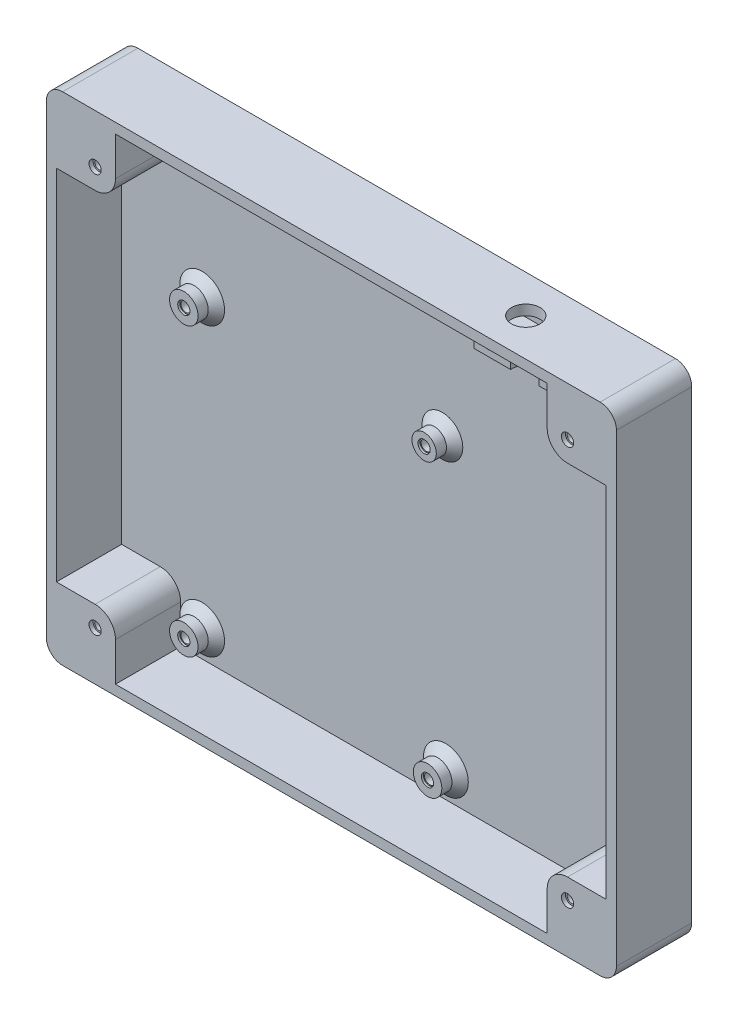
SolidWorks part; units mm, degrees
note: The reader was unsure of these and kept them because the rebuilt part matched: shared geometry of "Croquis1<10>", "Croquis1<11>", "Croquis1<12>", "Croquis1<13>", "Croquis1<14>", "Croquis1<17>".
ref_plane "Alzado" through (0, 0, 0) normal (0, 0, 1) x (1, 0, 0)
ref_plane "Planta" through (0, 0, 0) normal (0, 1, 0) x (1, 0, 0)
ref_plane "Vista lateral" through (0, 0, 0) normal (1, 0, 0) x (0, 0, -1)
sketch "Croquis1" plane through (0, 0, 0) normal (0, 0, 1) x (1, 0, 0)
  line L0 (-40.3571, 102.7463) -> (26.6429, 102.7463)
  line L5 (-40.3571, 102.7463) -> (-40.3571, 24.7463)
  line L6 (-40.3571, 24.7463) -> (26.6429, 24.7463)
  line L7 (26.6429, 102.7463) -> (26.6429, 24.7463)
  line L8 (-40.3571, 102.7463) -> (-34.5972, 102.7463)
  line L9 (26.6429, 102.7463) -> (21.034, 102.7463)
  line L10 (26.6429, 102.7463) -> (26.6429, 99.4658)
  line L11 (26.6429, 24.7463) -> (20.7429, 24.7463)
  line L12 (26.6429, 24.7463) -> (26.6429, 27.9463)
  line L13 (-40.3571, 102.7463) -> (-40.3571, 99.2397)
  line L14 (-40.3571, 24.7463) -> (-34.4345, 24.7463)
  line L15 (-40.3571, 24.7463) -> (-40.3571, 28.5815)
  line L16 (11.3637, 142.2045) -> (11.3637, 20.2045) construction
  line L17 (-41.6363, 129.7045) -> (-41.6363, 141.7045)
  line L26 (-59.1363, 80.7045) -> (80.8637, 80.7045) construction
  line L27 (69.3637, 124.7045) -> (81.3637, 124.7045)
  line L28 (64.3637, 129.7045) -> (64.3637, 141.7045)
  line L29 (69.3637, 36.7045) -> (81.3637, 36.7045)
  line L30 (64.3637, 31.7045) -> (64.3637, 19.7045)
  line L31 (-46.6363, 36.7045) -> (-58.6363, 36.7045)
  line L32 (-41.6363, 31.7045) -> (-41.6363, 19.7045)
  line L39 (81.3637, 137.7045) -> (81.3637, 23.7045)
  line L48 (37.3657, 131.6408) -> (62.3657, 131.6408) construction
  line L53 (37.3657, 134.6408) -> (62.3657, 134.6408)
  line L54 (37.3657, 134.6408) -> (37.3657, 128.6408)
  line L59 (37.3657, 128.6408) -> (62.3657, 128.6408)
  line L60 (62.3657, 134.6408) -> (62.3657, 128.6408)
  line L61 (37.3657, 134.6408) -> (62.3657, 128.6408) construction
  line L62 (37.3657, 128.6408) -> (62.3657, 134.6408) construction
  line L63 (77.3637, 141.7045) -> (-54.6363, 141.7045)
  line L65 (-54.6363, 19.7045) -> (77.3637, 19.7045)
  line L66 (-58.6363, 137.7045) -> (-58.6363, 23.7045)
  line L67 (-46.6363, 124.7045) -> (-58.6363, 124.7045)
  circle A0 centre (22.6429, 99.1463) radius 1.25
  circle A1 centre (22.6429, 99.1463) radius 3
  circle A2 centre (23.4929, 28.6463) radius 1.25
  circle A3 centre (23.4929, 28.6463) radius 3.5
  circle A4 centre (-36.3571, 99.1463) radius 1.25
  circle A5 centre (-36.3571, 99.1463) radius 3.5
  circle A6 centre (-36.3571, 28.7463) radius 3.5
  circle A7 centre (-36.3571, 28.7463) radius 1.25
  circle A8 centre (-36.3571, 28.7463) radius 1.5
  circle A9 centre (23.4929, 28.6463) radius 1.5
  circle A10 centre (22.6429, 99.1463) radius 1.5
  circle A11 centre (-36.3571, 99.1463) radius 1.5
  circle A12 centre (-46.6363, 129.7045) radius 1.5
  circle A13 centre (-46.6363, 129.7045) radius 1.1
  arc A15 (-46.6363, 124.7045) -> (-41.6363, 129.7045) centre (-46.6363, 129.7045) ccw
  circle A16 centre (69.3637, 129.7045) radius 1.1
  circle A17 centre (69.3637, 129.7045) radius 1.5
  arc A18 (69.3637, 124.7045) -> (64.3637, 129.7045) centre (69.3637, 129.7045) cw
  circle A19 centre (69.3637, 31.7045) radius 1.5
  circle A20 centre (69.3637, 31.7045) radius 1.1
  arc A21 (69.3637, 36.7045) -> (64.3637, 31.7045) centre (69.3637, 31.7045) ccw
  circle A22 centre (-46.6363, 31.7045) radius 1.5
  circle A23 centre (-46.6363, 31.7045) radius 1.1
  arc A24 (-46.6363, 36.7045) -> (-41.6363, 31.7045) centre (-46.6363, 31.7045) cw
  circle A29 centre (40.8657, 131.6408) radius 1.5
  circle A30 centre (58.8657, 131.6408) radius 1.5
  arc A31 (81.3637, 23.7045) -> (77.3637, 19.7045) centre (77.3637, 23.7045) cw
  arc A32 (-58.6363, 23.7045) -> (-54.6363, 19.7045) centre (-54.6363, 23.7045) ccw
  arc A33 (81.3637, 137.7045) -> (77.3637, 141.7045) centre (77.3637, 137.7045) ccw
  arc A34 (-58.6363, 137.7045) -> (-54.6363, 141.7045) centre (-54.6363, 137.7045) cw
  circle A35 centre (40.8657, 131.6408) radius 1.25
  circle A36 centre (58.8657, 131.6408) radius 1.25
  point P5 (-7.7063, 62.7578)
  point P77 (11.3637, 81.2045)
  point P82 (49.8657, 131.6408)
  point P90 (49.8657, 131.6408)
  point P95 (49.8657, 131.6408)
  dimension "D14" = 140
  dimension "D3" = 67
  dimension "D4" = 3.15
  dimension "D5" = 4
  dimension "D6" = 3.9
  dimension "D7" = 4
  dimension "D8" = 3.6
  dimension "D9" = 4
  dimension "D10" = 17
  dimension "D12" = 122
  dimension "D17" = 25
  dimension "D18" = 6
  dimension "D19" = 3
  dimension "D20" = 3
  dimension "D21" = 12
  dimension "D22" = 5
  dimension "D24" = 4
extrude "Saliente-Extruir5" add sketch "Croquis1" along normal blind 18.5 contours L31 A24 L32 L65 L30 A21 L29 L39 L27 A18 L28 L63 L17 A15 L67 L66 A3 L12 L6 L5 L0 L7 L53 L60 L59 L54 | A3 L7 L0 L5 L6 L12 A6 A5 A1 | A4 | A11 A4 | A5 A11 | A13 | A12 A13 | A34 L66 L67 A15 L17 L63 A12 | L39 A33 L63 L28 A18 L27 A17 | A17 A16 | A16 | L60 L53 L54 L59 A30 A29 | A36 | A30 A36 | A35 | A29 A35 | A10 A0 | A1 A10 | A0 | A22 A23 | A23 | L66 A32 L65 L32 A24 L31 A22 | A6 A8 | A8 A7 | A7 | L7 A3 A9 | L7 A3 | A2 | A9 A2 | A31 L39 L29 A21 L30 L65 A19 | A19 A20 | A20
shell "Vaciado3" thickness 2.5
extrude "Saliente-Extruir6" add sketch "Croquis1<10>" along normal blind 18.5
sketch "Croquis1<10>" plane through (0, 0, 0) normal (0, 0, 1) x (1, 0, 0) same geometry as "Croquis1"
extrude "Saliente-Extruir7" add sketch "Croquis1<11>" along normal blind 4.5 from surface at 2.5 contours A6 A8 | L7 A3 A9 | A1 A10 | A5 A11 | L7 A3
sketch "Croquis1<11>" plane through (0, 0, 0) normal (0, 0, 1) x (1, 0, 0) same geometry as "Croquis1"
chamfer "Chaflán1" distance 2 angle 45 4 edges at (-32.8571, 28.7463, 2.5) (25.6429, 99.1463, 2.5) (-32.8571, 99.1463, 2.5) (26.9929, 28.6463, 2.5)
extrude "Saliente-Extruir8" add sketch "Croquis1<12>" along normal blind 7 from surface at 2.5 contours L60 L53 L54 L59 A30 A29
sketch "Croquis1<12>" plane through (0, 0, 0) normal (0, 0, 1) x (1, 0, 0) same geometry as "Croquis1"
sketch "Croquis3" plane through (0, 0, 0) normal (0, 1, 0) x (1, 0, 0)
  line L9 (81.3637, 0) -> (-58.6363, 0)
  line L10 (81.3637, 0) -> (81.3637, -18.5)
  line L11 (81.3637, -18.5) -> (-58.6363, -18.5)
  line L12 (-58.6363, 0) -> (-58.6363, -18.5)
  line L13 (81.3637, 0) -> (49.8637, 0)
  line L14 (81.3637, 0) -> (81.3637, -9.25)
  line L15 (81.3637, -9.25) -> (49.8637, -9.25)
  line L16 (49.8637, 0) -> (49.8637, -9.25)
  circle A1 centre (49.8637, -9.25) radius 3.5
  dimension "D1" = 9.25
  dimension "D2" = 31.5
extrude "Saliente-Extruir9" add sketch "Croquis1<13>" along normal blind 17.5 contours A17 A16 | A12 | A13 | A22 | A23 | A19 | A20
sketch "Croquis1<13>" plane through (0, 0, 0) normal (0, 0, 1) x (1, 0, 0) same geometry as "Croquis1"
extrude "Saliente-Extruir10" add sketch "Croquis1<14>" along normal blind 4 from surface at 2.5 contours A8 A7 | A9 A2 | A10 A0 | A11 A4 starting at face at (60.3657, 131.6408, 2.5)
sketch "Croquis1<14>" plane through (0, 0, 0) normal (0, 0, 1) x (1, 0, 0) same geometry as "Croquis1"
extrude "Cortar-Extruir2" cut sketch "Croquis3" against normal blind 13.5 from surface at 141.7045 contours L16 A1 L15 | L15 A1 L16 starting at face at (11.3637, 141.7045, 9.25)
extrude "Saliente-Extruir12" add sketch "Croquis1<17>" along normal blind 9 contours A29 A35 | A30 A36
sketch "Croquis1<17>" plane through (0, 0, 0) normal (0, 0, 1) x (1, 0, 0) same geometry as "Croquis1"
